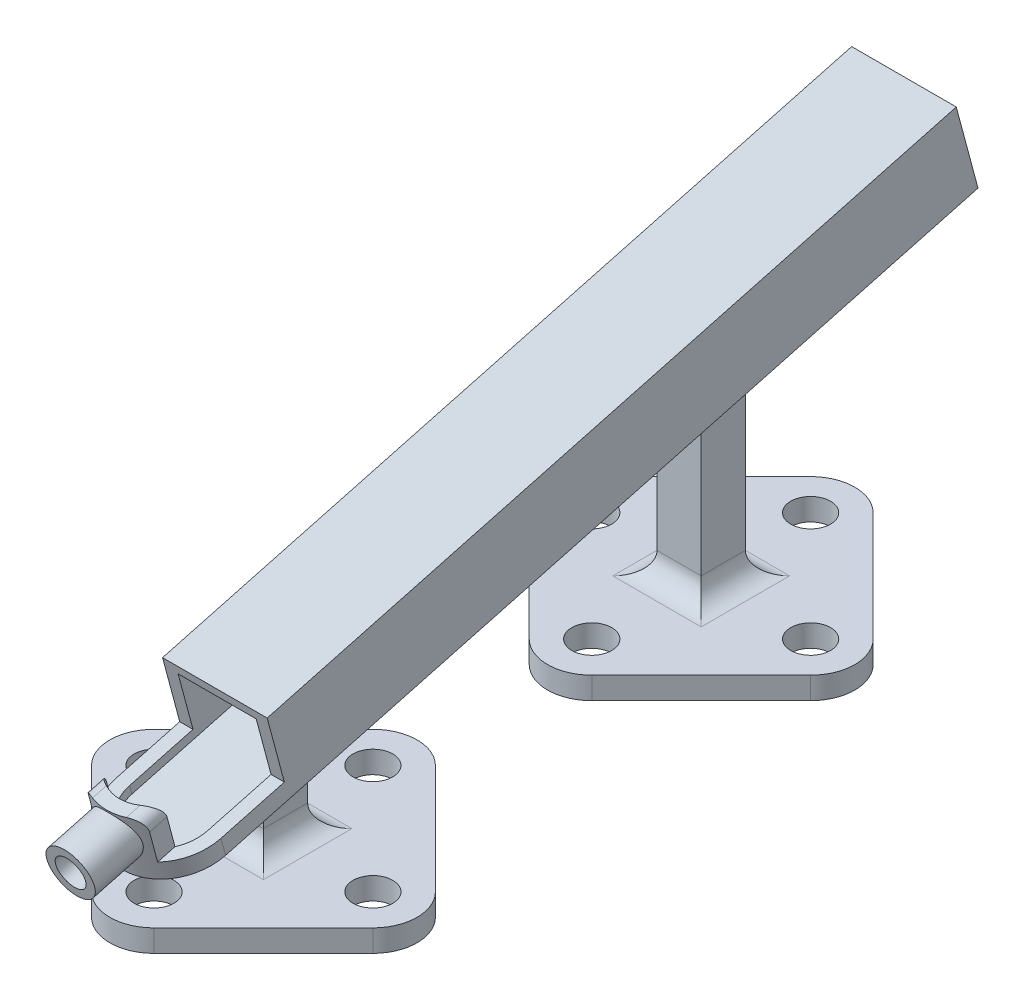
SolidWorks part; units mm, degrees
ref_plane "Front" through (0, 0, 0) normal (0, 0, 1) x (1, 0, 0)
ref_plane "Top" through (0, 0, 0) normal (0, 1, 0) x (1, 0, 0)
ref_plane "Right" through (0, 0, 0) normal (1, 0, 0) x (0, 0, -1)
ref_axis "Axis1" through (0, 55, 0) along (0, -1, 0)
ref_axis "Axis2" through (88.99, 0, 0) along (-1, 0, 0)
ref_axis "Axis3" through (0, 0, 55) along (0, 0, -1)
sketch "Sketch1" plane through (0, 0, 0) normal (0, 1, 0) x (1, 0, 0)
  line L0 (-24.75, 0) -> (0, 24.75) construction
  line L9 (-24.75, 0) -> (0, -24.75) construction
  line L11 (0, 24.75) -> (24.75, 0) construction
  line L12 (0, -24.75) -> (24.75, 0) construction
  line L13 (-24.75, 0) -> (24.75, 0) construction
  line L14 (0, 24.75) -> (0, -24.75) construction
  line L15 (-31.8211, 7.0711) -> (-7.0711, 31.8211)
  line L16 (7.0711, 31.8211) -> (31.8211, 7.0711)
  line L17 (7.0711, -31.8211) -> (31.8211, -7.0711)
  line L18 (-31.8211, -7.0711) -> (-7.0711, -31.8211)
  line L19 (0, -38.8921) -> (38.8921, 0) construction
  line L20 (-38.8921, 0) -> (0, -38.8921) construction
  line L21 (0, 38.8921) -> (38.8921, 0) construction
  line L22 (-38.8921, 0) -> (0, 38.8921) construction
  arc A4 (7.0711, -31.8211) -> (-7.0711, -31.8211) centre (0, -24.75) cw
  arc A5 (31.8211, 7.0711) -> (31.8211, -7.0711) centre (24.75, 0) cw
  arc A6 (-7.0711, 31.8211) -> (7.0711, 31.8211) centre (0, 24.75) cw
  arc A7 (-31.8211, 7.0711) -> (-31.8211, -7.0711) centre (-24.75, 0) ccw
  circle A8 centre (0, 24.75) radius 4.5
  circle A9 centre (24.75, 0) radius 4.5
  circle A10 centre (0, -24.75) radius 4.5
  circle A11 centre (-24.75, 0) radius 4.5
  point P1 (0, 0)
  dimension "D3" = 10
  dimension "D4" = 9
  dimension "D1" = 49.5
  dimension "D2" = 10
extrude "Boss-Extrude1" add sketch "Sketch1" along normal mid plane 5
ref_plane "Plane1" through (0, 0, 49.5) normal (0, 0, 1) x (1, 0, 0)
mirror "Mirror3" about plane through (0, 0, 49.5) normal (0, 0, 1) of bodies 101
sketch "Sketch2" plane through (0, 0, 0) normal (1, 0, 0) x (0, 0, -1)
  line L0 (-106.0711, 2.5) -> (-130.8211, 2.5) construction
  line L1 (-104, 2.5) -> (-94, 2.5)
  line L2 (-104, 2.5) -> (-104, 47.5)
  line L3 (-104, 47.5) -> (-94, 47.5)
  line L4 (-94, 2.5) -> (-94, 47.5)
  line L5 (-106.0711, -2.5) -> (-91.9289, -2.5) construction
  line L6 (-67.1789, -2.5) -> (-91.9289, -2.5) construction
  point P8 (-99, -2.5)
  point P9 (-99, 47.5)
  dimension "D1" = 10
  dimension "D2" = 50
extrude "Boss-Extrude2" add sketch "Sketch2" along normal mid plane 10 separate body
mirror "Mirror5" about plane through (0, 0, 49.5) normal (0, 0, 1) of bodies 103
sketch "Sketch3" plane through (0, 0, 0) normal (1, 0, 0) x (0, 0, -1)
  line L0 (-104, 17.5) -> (5, 46.7065)
  line L1 (-67.1789, -2.5) -> (-91.9289, -2.5) construction
  line L2 (-104, 47.5) -> (-104, 2.5) construction
  line L3 (-106.0711, 2.5) -> (-130.8211, 2.5) construction
  line L4 (5, 47.5) -> (5, 2.5) construction
  point P6 (-104, 17.5)
  dimension "D1" = 15
  dimension "D2" = 15
extrude "Cut-Extrude1" cut sketch "Sketch3" against normal through all both and the other way through all
sketch "Sketch4" plane through (0, 0, 0) normal (1, 0, 0) x (0, 0, -1)
  line L0 (-130.8211, 10.3133) -> (14.0678, 49.1362)
  line L1 (-130.8211, 10.3133) -> (-131.3387, 12.2452)
  line L2 (14.0678, 49.1362) -> (13.5502, 51.068)
  line L3 (-131.3387, 12.2452) -> (13.5502, 51.068)
  line L6 (-104, 17.5) -> (-94, 20.1795) construction
  dimension "D1" = 2
  dimension "D2" = 150
extrude "Boss-Extrude3" add sketch "Sketch4" along normal mid plane 23.66 separate body
combine bodies "Combine1" operation type add bodies to combine 102 106
combine bodies "Combine2" operation type add bodies to combine 107 101
fillet "Fillet1" radius 5 4 edges at (0, 2.5, 94) (-5, 2.5, 99) (0, 2.5, 104) (5, 2.5, 99)
fillet "Fillet2" radius 5 4 edges at (0, 2.5, 5) (0, 2.5, -5) (-5, 2.5, 0) (5, 2.5, 0)
sketch "Sketch5" plane through (0, 44.2596, 11.8593) normal (0, 0.9659, 0.2588) x (1, 0, 0)
  line L0 (11.83, -111.8642) -> (0, -111.8642) construction
  line L1 (11.83, 26.3058) -> (11.83, -123.6942) construction
  line L2 (0, -111.8642) -> (0, -123.6942) construction
  line L3 (11.83, -123.6942) -> (-11.83, -123.6942) construction
  line L4 (-11.83, -111.8642) -> (-11.83, -123.6942)
  line L5 (-11.83, -123.6942) -> (0, -123.6942)
  line L6 (0, -123.6942) -> (11.83, -123.6942)
  line L7 (11.83, -123.6942) -> (11.83, -111.8642)
  circle A0 centre (0, -111.8642) radius 8.73 construction
  circle A1 centre (0, -111.8642) radius 8.83
  circle A2 centre (0, -111.8642) radius 11.83
  line M3 (-11.83, 26.3058) -> (-11.83, -123.6942)
  line M4 (-11.83, -123.6942) -> (11.83, -123.6942)
  line M5 (11.83, -123.6942) -> (11.83, 26.3058)
  dimension "D1" = 17.46
  dimension "D2" = 0.1
  dimension "D3" = 3
extrude "Cut-Extrude4" cut sketch "Sketch5" against normal up to next (2 mm away) contours A2 M3 M4 | A2 M4 M5 region at (-9.1876, 12.9291, 128.7863) region at (9.1876, 12.9291, 128.7863)
sketch "Sketch6" plane through (0, 44.2596, 11.8593) normal (0, 0.9659, 0.2588) x (1, 0, 0)
  line L6 (8.83, -111.8642) -> (8.83, 23.3058)
  line L7 (8.83, 23.3058) -> (-8.83, 23.3058)
  line L8 (-8.83, 23.3058) -> (-8.83, -111.8642)
  line L9 (8.83, -111.8642) -> (8.83, 23.3058)
  line L10 (8.83, 23.3058) -> (-8.83, 23.3058)
  line L11 (-8.83, 23.3058) -> (-8.83, -111.8642)
  line L12 (11.83, -111.8642) -> (11.83, 26.3058)
  line L13 (11.83, 26.3058) -> (-11.83, 26.3058)
  line L14 (-11.83, 26.3058) -> (-11.83, -111.8642)
  line L15 (11.83, -111.8642) -> (11.83, 26.3058)
  line L16 (11.83, 26.3058) -> (-11.83, 26.3058)
  line L17 (-11.83, 26.3058) -> (-11.83, -111.8642)
  arc A2 (-8.83, -111.8642) -> (8.83, -111.8642) centre (0, -111.8642) ccw
  arc A3 (-8.83, -111.8642) -> (8.83, -111.8642) centre (0, -111.8642) ccw
  arc A4 (-11.83, -111.8642) -> (11.83, -111.8642) centre (0, -111.8642) ccw
  arc A5 (-11.83, -111.8642) -> (11.83, -111.8642) centre (0, -111.8642) ccw
  dimension "D1" = 3
  dimension "D2" = 0
extrude "Boss-Extrude4" add sketch "Sketch6" along normal blind 12
sketch "Sketch7" plane through (0, 55.8507, 14.9651) normal (0, 0.9659, 0.2588) x (1, 0, 0)
  line L1 (-11.83, -97.0342) -> (-8.83, -97.0342)
  line L2 (-8.83, 23.3058) -> (-8.83, -111.8642) construction
  line L3 (11.83, -111.8642) -> (11.83, 26.3058)
  line L4 (11.83, 26.3058) -> (-11.83, 26.3058)
  line L5 (-11.83, 26.3058) -> (-11.83, -111.8642)
  line L6 (11.83, -97.0342) -> (11.83, 26.3058)
  line L7 (11.83, 26.3058) -> (-11.83, 26.3058)
  line L8 (-11.83, 26.3058) -> (-11.83, -97.0342)
  line L10 (8.83, -111.8642) -> (8.83, 23.3058) construction
  line L11 (8.83, -97.0342) -> (11.83, -97.0342)
  line L12 (8.83, 23.3058) -> (-8.83, 23.3058) construction
  line L13 (8.83, 23.3058) -> (-8.83, 23.3058)
  line L14 (-8.83, 23.3058) -> (-8.83, -97.0342)
  line L15 (8.83, -97.0342) -> (8.83, 23.3058)
  arc A1 (-11.83, -111.8642) -> (11.83, -111.8642) centre (0, -111.8642) ccw
  arc A4 (-8.83, -111.8642) -> (8.83, -111.8642) centre (0, -111.8642) ccw construction
  dimension "D2" = 6
  dimension "D1" = 0
extrude "Boss-Extrude5" add sketch "Sketch7" along normal blind 5
sketch "Sketch8" plane through (0, 0, 0) normal (1, 0, 0) x (0, 0, -1)
  line L0 (-109.987, 35.566) -> (-109.4694, 33.6342)
  line L1 (-109.987, 35.566) -> (-108.693, 30.7364) construction
  line L2 (-109.4694, 33.6342) -> (9.6679, 65.5569)
  line L3 (14.0678, 49.1362) -> (9.1502, 67.4888) construction
  line L4 (9.6679, 65.5569) -> (9.1502, 67.4888)
  line L5 (9.1502, 67.4888) -> (-109.987, 35.566)
  dimension "D1" = 2
extrude "Boss-Extrude6" add sketch "Sketch8" along normal up to next and the other way up to next
sketch "Sketch9" plane through (0, 6.032, -22.5117) normal (0, -0.2588, 0.9659) x (1, 0, 0)
  line L4 (8.83, 60.8209) -> (-8.83, 60.8209)
  line L5 (-8.83, 60.8209) -> (-8.83, 45.8209)
  line L6 (-8.83, 45.8209) -> (8.83, 45.8209)
  line L7 (8.83, 45.8209) -> (8.83, 60.8209)
  line L8 (8.83, 60.8209) -> (-8.83, 60.8209)
  line L9 (-8.83, 60.8209) -> (-8.83, 45.8209)
  line L10 (-8.83, 45.8209) -> (8.83, 45.8209)
  line L11 (8.83, 45.8209) -> (8.83, 60.8209)
  dimension "D1" = 0
extrude "Cut-Extrude5" cut sketch "Sketch9" against normal through all
sketch "Sketch10" plane through (0, 55.8507, 14.9651) normal (0, 0.9659, 0.2588) x (1, 0, 0)
  line L0 (-11.83, -97.0342) -> (-11.83, -111.8642) construction
  line L1 (-6.83, -97.0342) -> (-16.83, -97.0342)
  line L2 (-6.83, -97.0342) -> (-6.83, -126.6942)
  line L3 (-6.83, -126.6942) -> (-16.83, -126.6942)
  line L4 (-16.83, -97.0342) -> (-16.83, -126.6942)
  line L5 (-6.83, -97.0342) -> (-16.83, -126.6942) construction
  line L6 (-6.83, -126.6942) -> (-16.83, -97.0342) construction
  line L7 (-11.83, -97.0342) -> (11.83, -97.0342) construction
  point P0 (-11.83, -111.8642)
  dimension "D2" = 10
extrude "Cut-Extrude6" cut sketch "Sketch10" against normal blind 10
mirror "Mirror6" about plane through (0, 0, 0) normal (1, 0, 0) of "Cut-Extrude6"
ref_plane "Plane2" through (0, -32.0144, 119.4794) normal (0, -0.2588, 0.9659) x (1, 0, 0)
sketch "Sketch11" plane through (0, -32.0144, 119.4794) normal (0, -0.2588, 0.9659) x (1, 0, 0)
  line L1 (6.83, 57.8209) -> (-6.83, 57.8209) construction
  circle A0 centre (0, 52.0209) radius 3.4
  circle A1 centre (0, 52.0209) radius 5.4
  point P8 (0, 57.8209)
  dimension "D1" = 6.8
  dimension "D3" = 5.8
  dimension "D2" = 2
extrude "Boss-Extrude8" add sketch "Sketch11" along normal blind 10 and the other way up to surface other way up to face at (0, 16.9454, 127.3202)
sketch "Sketch12" plane through (0, -34.6026, 129.1386) normal (0, -0.2588, 0.9659) x (1, 0, 0)
  circle A0 centre (0, 52.0209) radius 3.4 construction
  circle A1 centre (0, 52.0209) radius 3.4
extrude "Cut-Extrude7" cut sketch "Sketch12" against normal up to next
fillet "Fillet3" radius 3 2 edges at (6.83, 24.9239, 130.3855) (-6.83, 24.9239, 130.3855)
sketch "Sketch13" plane through (0, 6.8085, -25.4095) normal (0, 0.2588, -0.9659) x (-1, 0, 0)
  line L0 (8.83, 45.8209) -> (-8.83, 45.8209) construction
  line L1 (8.83, 60.8209) -> (8.83, 45.8209) construction
  line L2 (-8.83, 45.8209) -> (-8.83, 60.8209) construction
  line L3 (-8.83, 60.8209) -> (8.83, 60.8209) construction
  line L4 (11.83, 43.8209) -> (11.83, 62.8209)
  line L5 (11.83, 62.8209) -> (-11.83, 62.8209)
  line L6 (-11.83, 62.8209) -> (-11.83, 43.8209)
  line L7 (-11.83, 43.8209) -> (11.83, 43.8209)
  line L8 (11.83, 43.8209) -> (11.83, 62.8209)
  line L9 (11.83, 62.8209) -> (-11.83, 62.8209)
  line L10 (-11.83, 62.8209) -> (-11.83, 43.8209)
  line L11 (-11.83, 43.8209) -> (11.83, 43.8209)
  line L12 (8.83, 45.8209) -> (-8.83, 45.8209)
  line L13 (8.83, 60.8209) -> (8.83, 45.8209)
  line L14 (-8.83, 45.8209) -> (-8.83, 60.8209)
  line L15 (-8.83, 60.8209) -> (8.83, 60.8209)
  dimension "D1" = 0
extrude "Boss-Extrude9" add sketch "Sketch13" along normal blind 38
